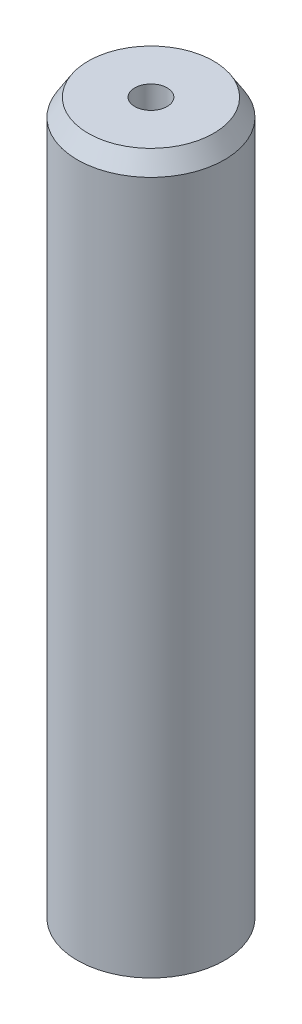
SolidWorks part; units mm, degrees
ref_plane "Front Plane" through (0, 0, 0) normal (0, 0, 1) x (1, 0, 0)
ref_plane "Top Plane" through (0, 0, 0) normal (0, 1, 0) x (1, 0, 0)
ref_plane "Right Plane" through (0, 0, 0) normal (1, 0, 0) x (0, 0, -1)
sketch "Sketch1" plane through (0, 0, 0) normal (0, 1, 0) x (1, 0, 0)
  circle A0 centre (0, 0) radius 5
  dimension "SHAFT_OD" = 10
extrude "Boss-Extrude1" add sketch "Sketch1" along normal blind 49.0385
sketch "Sketch2" plane through (0, 0, 0) normal (0, 1, 0) x (1, 0, 0)
  circle A0 centre (0, 0) radius 1.1014
  dimension "BORE_D" = 2.2027
extrude "Cut-Extrude1" cut sketch "Sketch2" along normal through all
chamfer "Chamfer1" distance 1.1853 angle 31.973 2 edges at (0, 49.0385, 5) (0, 0, 5) first distance on face at (0, 49.0385, 5) first distance on face at (0, 0, 1.1014)
